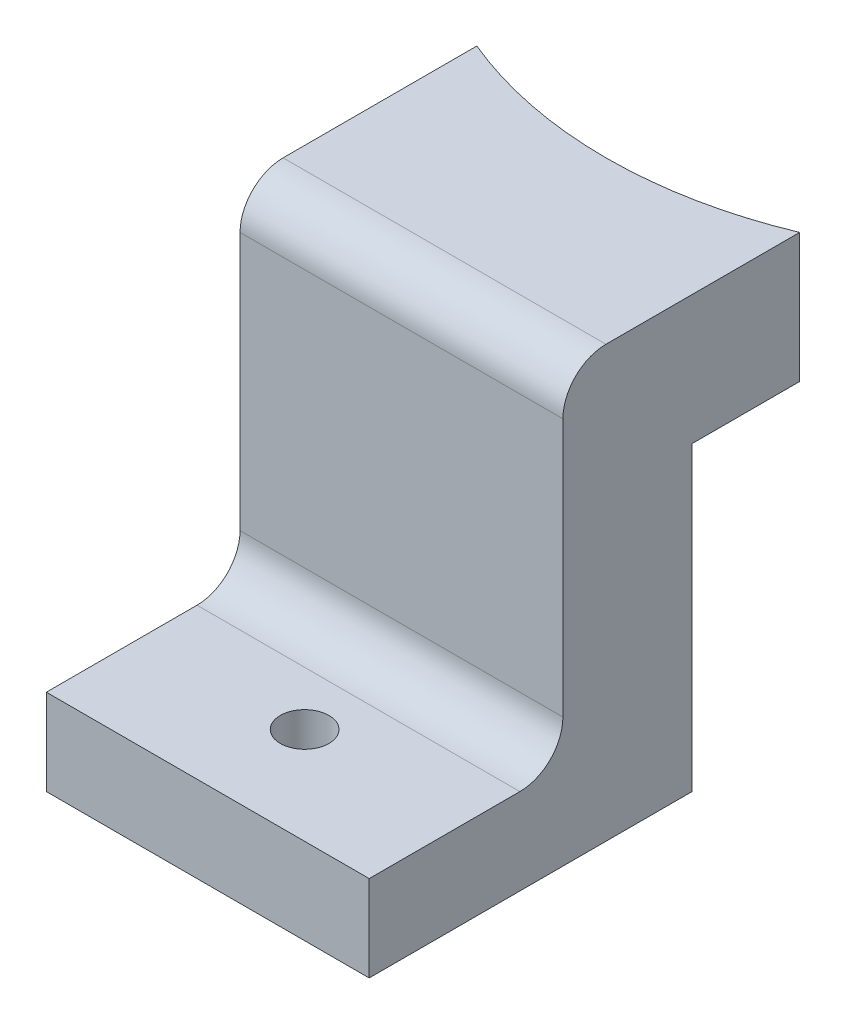
SolidWorks part; units mm, degrees
material "6061 Alloy"
ref_plane "Front Plane" through (0, 0, 0) normal (0, 0, 1) x (1, 0, 0)
ref_plane "Top Plane" through (0, 0, 0) normal (0, 1, 0) x (1, 0, 0)
ref_plane "Right Plane" through (0, 0, 0) normal (1, 0, 0) x (0, 0, -1)
sketch "Sketch1" plane through (0, 0, 0) normal (0, 1, 0) x (1, 0, 0)
  line L0 (7.5, 5) -> (-7.5, -5) construction
  line L1 (-7.5, 5) -> (7.5, 5)
  line L2 (-7.5, 5) -> (-7.5, -5)
  line L3 (-7.5, -5) -> (7.5, -5)
  line L4 (7.5, 5) -> (7.5, -5)
  line L5 (-7.5, 5) -> (7.5, -5) construction
  point P2 (0, 0)
  dimension "D1" = 15
  dimension "D2" = 10
extrude "Boss-Extrude1" add sketch "Sketch1" along normal blind 6
sketch "Sketch2" plane through (0, 6, 0) normal (0, 1, 0) x (1, 0, 0)
  circle A0 centre (0, 23) radius 19.5
  dimension "D1" = 39
extrude "Cut-Extrude1" cut sketch "Sketch2" against normal blind 9
sketch "Sketch3" plane through (0, 6, 0) normal (0, 1, 0) x (1, 0, 0)
  line L0 (-7.5, 5) -> (-7.5, -5) construction
  line L1 (-7.5, 0) -> (7.5, 0)
  line L2 (-7.5, 0) -> (-7.5, -6)
  line L3 (-7.5, -6) -> (7.5, -6)
  line L4 (7.5, 0) -> (7.5, -6)
  line L5 (-7.5, -5) -> (7.5, -5) construction
  line L6 (7.5, -5) -> (7.5, 5) construction
  dimension "D1" = 5
  dimension "D2" = 0
  dimension "D3" = 15
  dimension "D4" = 6
extrude "Boss-Extrude2" add sketch "Sketch3" against normal blind 20
sketch "Sketch4" plane through (0, 0, 6) normal (0, 0, 1) x (1, 0, 0)
  line L0 (-7.5, -14) -> (7.5, -14) construction
  line L1 (-7.5, -10) -> (7.5, -10)
  line L2 (-7.5, -10) -> (-7.5, -14)
  line L3 (-7.5, -14) -> (7.5, -14)
  line L4 (7.5, -10) -> (7.5, -14)
  line L5 (7.5, -14) -> (7.5, 6) construction
  line L6 (-7.5, -14) -> (-7.5, 6) construction
  dimension "D1" = 4
  dimension "D3" = 0
extrude "Boss-Extrude3" add sketch "Sketch4" along normal blind 9
sketch "Sketch9" plane through (0, -14, 0) normal (0, -1, 0) x (1, 0, 0)
  line L0 (0, 15) -> (0, 0) construction
  line L1 (-7.5, 15) -> (7.5, 15) construction
  line L2 (7.5, 0) -> (-7.5, 0) construction
  line L3 (-7.5, 10.5) -> (7.5, 10.5) construction
  line L4 (-7.5, 0) -> (-7.5, 15) construction
  line L5 (7.5, 15) -> (7.5, 0) construction
  point P12 (0, 10.5)
  dimension "D1" = 4.5
hole_wizard "#4-40 Tapped Hole2" positions "Sketch10" profile "Sketch11" tap size "#4-40" standard "ANSI Inch"
sketch "Sketch10" plane through (0, -14, 0) normal (0, -1, 0) x (-1, 0, 0)
  point P0 (0, -10.5)
sketch "Sketch11" plane through (0, -14, 10.5) normal (1, 0, 0) x (0, 0, -1)
  line L0 (0, 0) -> (0, 8.2792)
  line L1 (0, 8.2792) -> (1.1303, 7.6)
  line L2 (1.1303, 7.6) -> (1.1303, 0)
  line L5 (1.1303, 0) -> (0, 0)
  line L10 (0, 8.2792) -> (-1.1303, 7.6) construction
  line L11 (0, -6.35) -> (0, 107.95) construction
  dimension "Tap Drill Dia." = 2.2606
  dimension "Tap Drill Depth" = 7.6
  dimension "Drill Angle" = 118
cosmetic thread "Hole Thread2" parameters "D1"=5.69, "D2"=2.8448
fillet "Fillet2" radius 2 2 edges at (0, 6, 6) (0, -10, 6)
